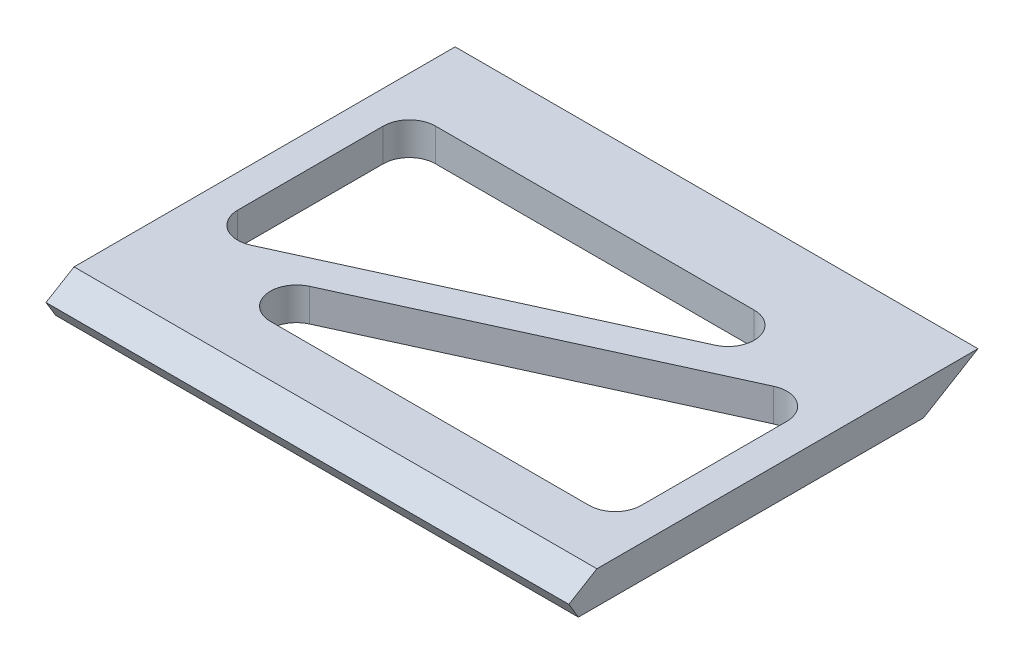
SolidWorks part; units mm, degrees
material "Balsa"
ref_plane "Front Plane" through (0, 0, 0) normal (0, 0, 1) x (1, 0, 0)
ref_plane "Top Plane" through (0, 0, 0) normal (0, 1, 0) x (1, 0, 0)
ref_plane "Right Plane" through (0, 0, 0) normal (1, 0, 0) x (0, 0, -1)
sketch "Sketch3" plane through (71.1933, 0, 0) normal (1, 0, 0) x (0, 0, -1)
  line L0 (56.968, 6.35) -> (46.3846, 0)
  line L1 (46.3846, 0) -> (-20.6804, 0)
  line L2 (-20.6804, 0) -> (-22.5302, 3.083)
  line L3 (-22.5302, 3.083) -> (-29.8236, 15.2385) construction
  line L4 (56.968, 6.35) -> (63.7199, 10.4011) construction
  line L6 (-22.5302, 3.083) -> (-17.0851, 6.35)
  line L7 (-17.0851, 6.35) -> (56.968, 6.35)
extrude "Boss-Extrude2" add sketch "Sketch3" against normal up to surface (101.6 mm away)
sketch "Sketch4" plane through (0, 6.35, 0) normal (0, 1, 0) x (1, 0, 0)
  line L0 (-30.4067, -17.0851) -> (-30.4067, 56.968) construction
  line L1 (-18.9767, 41.728) -> (42.949, 41.728)
  line L2 (-24.0567, 36.648) -> (-24.0567, 8.3732)
  line L3 (-2.1624, -7.1791) -> (59.7633, -7.1791)
  line L4 (64.8433, 26.1757) -> (64.8433, -2.0991)
  line L5 (-30.4067, 56.968) -> (71.1933, 56.968) construction
  line L6 (71.1933, 56.968) -> (71.1933, -17.0851) construction
  line L7 (-30.4067, -17.0851) -> (71.1933, -17.0851) construction
  line L8 (-16.8668, 3.7521) -> (45.0589, 32.0269)
  line L9 (-4.2724, 2.522) -> (57.6533, 30.7968)
  line L10 (-29.6117, -5.5575) -> (68.6464, 39.3064)
  arc A0 (-4.2724, 2.522) -> (-2.1624, -7.1791) centre (-2.1624, -2.0991) ccw
  arc A1 (59.7633, -7.1791) -> (64.8433, -2.0991) centre (59.7633, -2.0991) ccw
  arc A2 (57.6533, 30.7968) -> (64.8433, 26.1757) centre (59.7633, 26.1757) cw
  arc A3 (45.0589, 32.0269) -> (42.949, 41.728) centre (42.949, 36.648) ccw
  arc A4 (-18.9767, 41.728) -> (-24.0567, 36.648) centre (-18.9767, 36.648) ccw
  arc A5 (-16.8668, 3.7521) -> (-24.0567, 8.3732) centre (-18.9767, 8.3732) cw
  dimension "D7" = 5.08
  dimension "D1" = 6.35
  dimension "D2" = 15.24
  dimension "D3" = 6.35
  dimension "D4" = 9.906
  dimension "D5" = 3.175
  dimension "D6" = 3.175
extrude "Cut-Extrude1" cut sketch "Sketch4" against normal up to surface (6.35 mm away) contours A5 L8 A3 L1 A4 L2 | A2 L9 A0 L3 A1 L4 region at (4.1335, 6.35, -27.6167) region at (36.6531, 6.35, -6.9321) up to face at (20.3933, 0, -12.8521)
